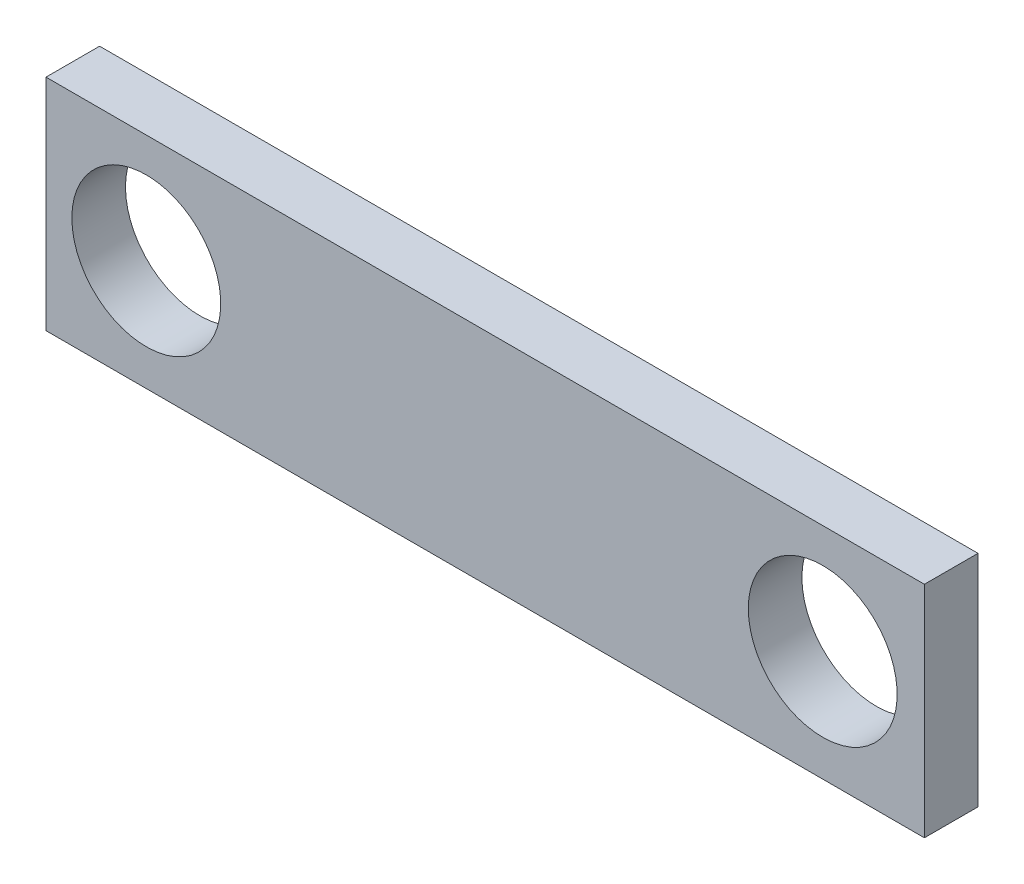
SolidWorks part; units mm, degrees
ref_plane "Plan de face" through (0, 0, 0) normal (0, 0, 1) x (1, 0, 0)
ref_plane "Plan de dessus" through (0, 0, 0) normal (0, 1, 0) x (1, 0, 0)
ref_plane "Plan de droite" through (0, 0, 0) normal (1, 0, 0) x (0, 0, -1)
sketch "Esquisse2" plane through (0, 0, 3) normal (0, 0, 1) x (1, 0, 0)
  line L1 (1.2382, -53.7991) -> (26.6382, -53.7991)
  line L2 (1.2382, -53.7991) -> (1.2382, -60.1491)
  line L3 (1.2382, -60.1491) -> (26.6382, -60.1491)
  line L4 (26.6382, -53.7991) -> (26.6382, -60.1491)
  dimension "D1" = 25.4
  dimension "D2" = 6.35
extrude "Boss.-Extru.1" add sketch "Esquisse2" along normal blind 1.55 contours L3 L4 L1 L2
hole_wizard "Dégagement #61" positions "Esquisse3" profile "Esquisse4" hole size "#6" standard "Ansi Inch" end condition through all
sketch "Esquisse3" plane through (0, 0, 3) normal (0, 0, -1) x (-1, 0, 0)
  line L0 (-1.2382, -53.7991) -> (-1.2382, -60.1491) construction
  line L1 (-1.2382, -60.1491) -> (-26.6382, -60.1491) construction
  point P0 (-4.1382, -56.9491)
  point P2 (-23.6982, -56.9491)
  dimension "D1" = 19.56
  dimension "D2" = 2.9
  dimension "D3" = 3.2
  dimension "D4" = 3.2
sketch "Esquisse4" plane through (4.1382, -56.9491, 3) normal (1, 0, 0) x (0, 1, 0)
  line L0 (0, 0) -> (0, 1.55)
  line L1 (0, 1.55) -> (2.1526, 1.55)
  line L2 (2.1526, 1.55) -> (2.1526, 0)
  line L5 (2.1526, 0) -> (0, 0)
  line L11 (0, -6.35) -> (0, 107.95) construction
  dimension "Diamètre du perçage jusqu'au prochain" = 4.3053
  dimension "Profondeur du perçage jusqu'au prochain" = 1.55
